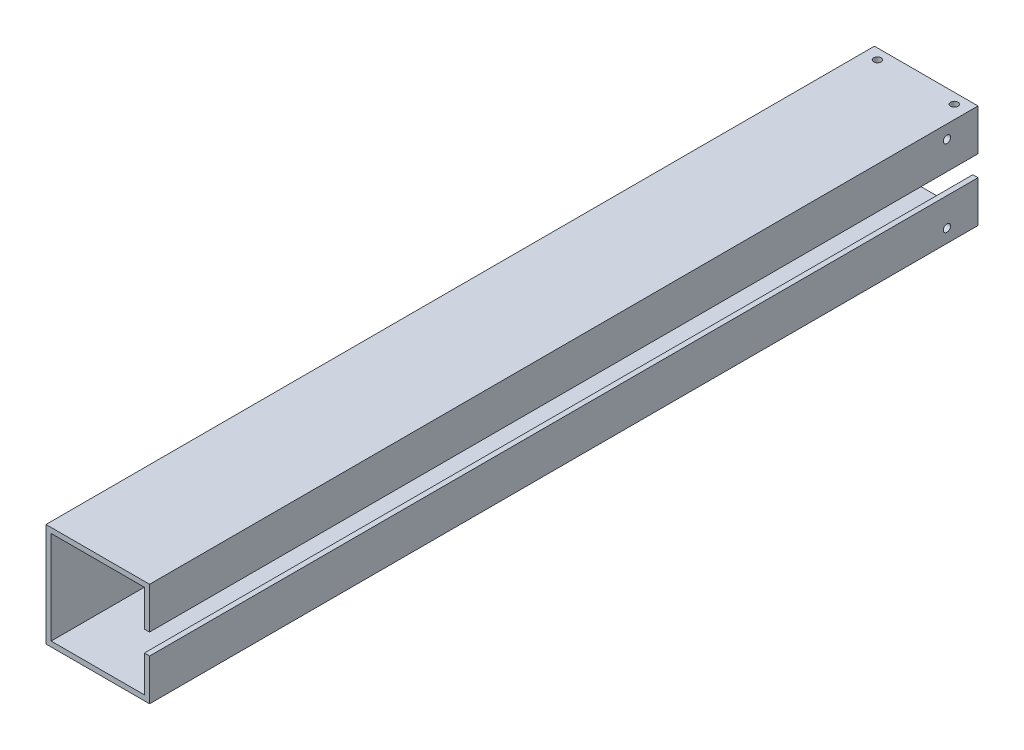
SolidWorks part; units mm, degrees
ref_plane "Front Plane" through (0, 0, 0) normal (1, 0, 0) x (0, 1, 0)
ref_plane "Top Plane" through (0, 0, 0) normal (0, 0, 1) x (0, 1, 0)
ref_plane "Right Plane" through (0, 0, 0) normal (0, 1, 0) x (-1, 0, 0)
sketch "Sketch1" plane through (0, 0, 0) normal (0, 0, 1) x (0, 1, 0)
  line L0 (28.575, -28.575) -> (28.575, 28.575)
  line L1 (31.75, -31.75) -> (-31.75, -31.75)
  line L2 (31.75, -31.75) -> (31.75, 31.75)
  line L3 (31.75, 31.75) -> (-31.75, 31.75)
  line L4 (-31.75, -31.75) -> (-31.75, 31.75)
  line L5 (31.75, -31.75) -> (-31.75, 31.75) construction
  line L6 (31.75, 31.75) -> (-31.75, -31.75) construction
  line L7 (28.575, 28.575) -> (-28.575, 28.575)
  line L8 (-28.575, -28.575) -> (-28.575, 28.575)
  line L9 (28.575, -28.575) -> (-28.575, -28.575)
  line L11 (6.35, -31.75) -> (-6.35, -31.75)
  line L12 (6.35, -31.75) -> (6.35, -28.575)
  line L13 (6.35, -28.575) -> (-6.35, -28.575)
  line L14 (-6.35, -31.75) -> (-6.35, -28.575)
  line L15 (6.35, -31.75) -> (-6.35, -28.575) construction
  line L16 (6.35, -28.575) -> (-6.35, -31.75) construction
  point P0 (0, 0)
  point P10 (0, -30.1625)
  dimension "D1" = 63.5
  dimension "D3" = 12.7
  dimension "D2" = 3.175
extrude "Boss-Extrude1" add sketch "Sketch1" along normal blind 508 contours L1 L14 L9 L8 L7 L0 L12 L2 L3 L4 region at (0, 29.473, 0)
sketch "Sketch2" plane through (0, 0, 0) normal (0, 1, 0) x (-1, 0, 0)
  line L0 (-28.575, 0) -> (28.575, 0) construction
  line L1 (-28.575, 0) -> (28.575, 0) construction
  line L2 (0, 0) -> (0, 508) construction
  line L3 (-31.75, 508) -> (31.75, 508) construction
  circle A0 centre (-23.575, 6.35) radius 5 construction
  circle A1 centre (-23.575, 6.35) radius 2.25
  circle A2 centre (23.575, 6.35) radius 2.25
  point P4 (-28.575, 6.35)
  point P5 (-18.575, 6.35)
  dimension "D1" = 10
  dimension "D2" = 4.5
  dimension "D3" = 6.35
extrude "Cut-Extrude1" cut sketch "Sketch2" against normal blind 254 and the other way blind 254
sketch "Sketch4" plane through (31.75, 0, 0) normal (1, 0, 0) x (0, 1, 0)
  line L0 (-28.575, 508) -> (-28.575, 0) construction
  line L1 (-28.575, 508) -> (-28.575, 0) construction
  line L2 (-6.35, 0) -> (-31.75, 0) construction
  line L3 (0, 0) -> (0, 508) construction
  line L4 (-6.35, 508) -> (-31.75, 508) construction
  circle A0 centre (-23.575, 19.05) radius 5 construction
  circle A1 centre (-23.575, 19.05) radius 2.25
  circle A2 centre (23.575, 19.05) radius 2.25
  point P12 (0, 0)
  dimension "D1" = 10
  dimension "D2" = 4.5
  dimension "D3" = 19.05
extrude "Cut-Extrude2" cut sketch "Sketch4" against normal blind 254
